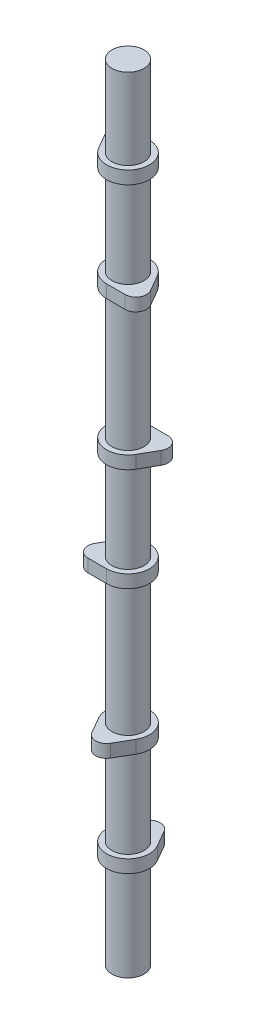
SolidWorks part; units mm, degrees
ref_plane "Front Plane" through (0, 0, 0) normal (0, 0, 1) x (1, 0, 0)
ref_plane "Top Plane" through (0, 0, 0) normal (0, 1, 0) x (1, 0, 0)
ref_plane "Right Plane" through (0, 0, 0) normal (1, 0, 0) x (0, 0, -1)
sketch "Sketch2" plane through (0, 0, 0) normal (0, 1, 0) x (1, 0, 0)
  line L0 (-5.4993, 15.875) -> (-10.9985, 6.35)
  line L1 (5.4993, 15.875) -> (10.9985, 6.35)
  arc A0 (-10.9985, 6.35) -> (10.9985, 6.35) centre (0, 0) ccw
  arc A1 (5.4993, 15.875) -> (-5.4993, 15.875) centre (0, 12.7) ccw
  dimension "D1" = 12.7
  dimension "D3" = 25.4
  dimension "D2" = 12.7
extrude "Boss-Extrude1" add sketch "Sketch2" along normal mid plane 7.62
ref_axis "Axis1" through (0, 85.2929, 0) along (0, -1, 0)
pattern_linear "LPattern1" count 2 spacing 60.96 along (0, 1, 0) of bodies 101
move or copy body "Body-Move/Copy1" bodies to move or copy 102 copy no rotation origin (0, 0, 0) rotation axis (0, 1, 0) rotation angle 180
pattern_linear "LPattern2" count 3 spacing 146.05 along (0, 1, 0) of bodies 101 103
move or copy body "Body-Move/Copy2" bodies to move or copy 104 106 copy no rotation origin (0, 0, 0) rotation axis (0, 1, 0) rotation angle 120
move or copy body "Body-Move/Copy3" bodies to move or copy 107 105 copy no rotation origin (0, 0, 0) rotation axis (0, -1, 0) rotation angle 120
sketch "Sketch5" plane through (0, 0, 0) normal (0, 1, 0) x (1, 0, 0)
  circle A0 centre (0, 0) radius 9.5
  dimension "D1" = 19
extrude "Boss-Extrude2" add sketch "Sketch5" along normal blind 464.25 from offset 59.53 offset against normal yes
equation "\"59.63.00mm\"=60"
